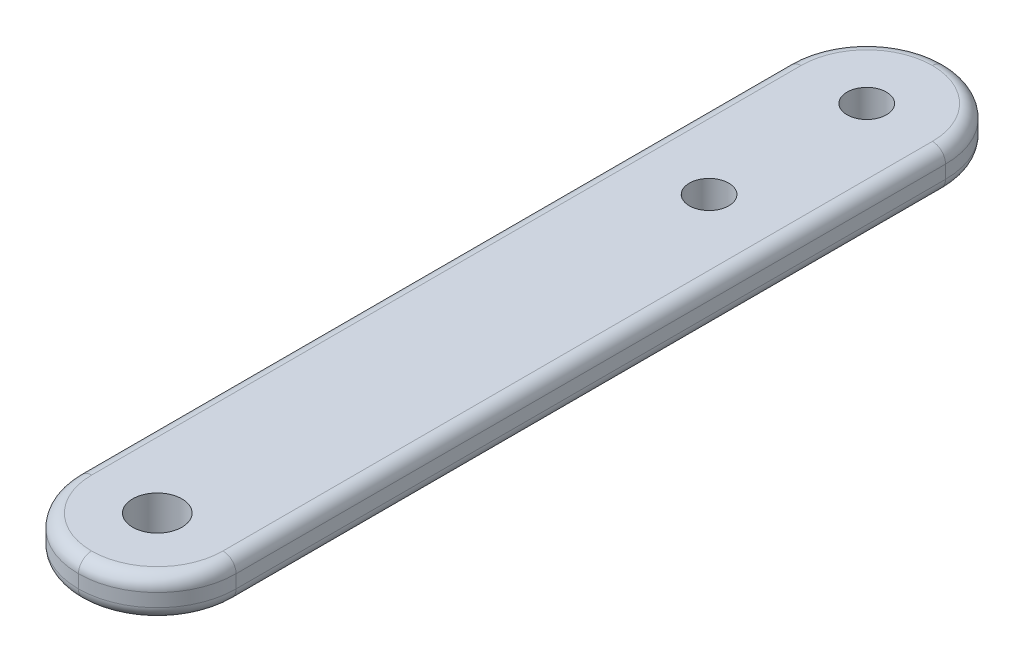
SolidWorks part; units mm, degrees
material "6061 Alloy"
ref_plane "Front Plane" through (0, 0, 0) normal (0, 0, 1) x (1, 0, 0)
ref_plane "Top Plane" through (0, 0, 0) normal (0, 1, 0) x (1, 0, 0)
ref_plane "Right Plane" through (0, 0, 0) normal (1, 0, 0) x (0, 0, -1)
sketch "Sketch1" plane through (0, 0, 0) normal (0, 1, 0) x (1, 0, 0)
  line L0 (0, 69.85) -> (0, -69.85) construction
  line L1 (-12.7, -69.85) -> (12.7, -69.85)
  line L2 (-12.7, -69.85) -> (-12.7, 69.85)
  line L3 (-12.7, 69.85) -> (12.7, 69.85)
  line L4 (12.7, -69.85) -> (12.7, 69.85)
  line L5 (-12.7, -69.85) -> (12.7, 69.85) construction
  line L6 (-12.7, 69.85) -> (12.7, -69.85) construction
  circle A0 centre (0, -57.15) radius 3.9687
  circle A1 centre (0, 31.75) radius 3.175
  circle A2 centre (0, 57.15) radius 3.175
  point P0 (0, 0)
  dimension "D3" = 6.35
  dimension "D1" = 7.9375
  dimension "D2" = 25.4
  dimension "D4" = 25.4
  dimension "D5" = 88.9
  dimension "D6" = 12.7
  dimension "D7" = 12.7
extrude "Boss-Extrude1" add sketch "Sketch1" along normal blind 6.35
fillet "Fillet2" radius 12.7 4 edges at (-12.7, 3.175, -69.85) (12.7, 3.175, -69.85) (-12.7, 3.175, 69.85) (12.7, 3.175, 69.85)
fillet "Fillet3" radius 2.1167 12 edges at (8.9803, 6.35, 66.1303) (-8.9803, 6.35, 66.1303) (-12.7, 6.35, 0) (-8.9803, 6.35, -66.1303) (8.9803, 6.35, -66.1303) (8.9803, 0, 66.1303) (-8.9803, 0, 66.1303) (-12.7, 0, 0) (-8.9803, 0, -66.1303) (8.9803, 0, -66.1303) (12.7, 6.35, 0) (12.7, 0, 0)
